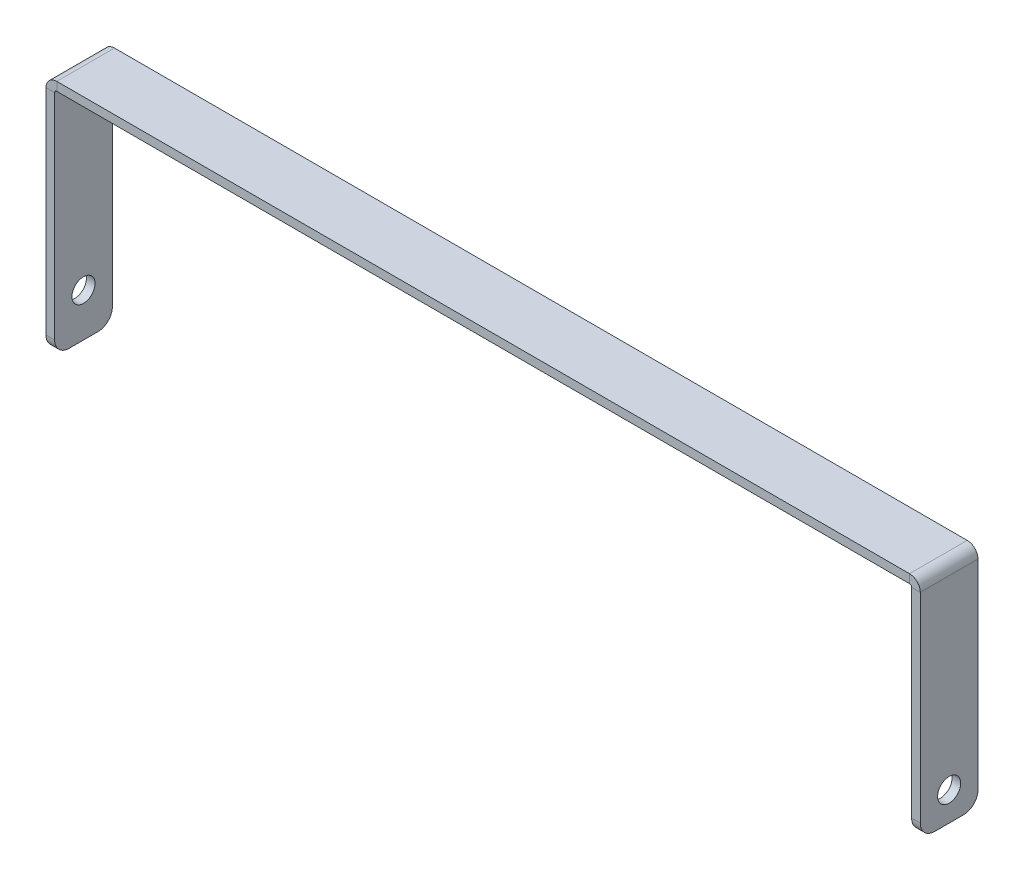
SolidWorks part; units mm, degrees
note: The reader was unsure of these and kept them because the rebuilt part matched: bend radius of "BaseBend1", "BaseBend2".
material "7079 Alloy"
ref_plane "Front" through (0, 0, 0) normal (0, 0, 1) x (1, 0, 0)
ref_plane "Top" through (0, 0, 0) normal (0, 1, 0) x (1, 0, 0)
ref_plane "Right" through (0, 0, 0) normal (1, 0, 0) x (0, 0, -1)
sketch "Sketch1" plane through (0, 0, 0) normal (0, 0, 1) x (1, 0, 0)
  line L0 (-148.5, -42.5) -> (-148.5, 37.5)
  line L1 (-148.5, 37.5) -> (148.5, 37.5)
  line L2 (148.5, 37.5) -> (148.5, -37.5)
  line L3 (148.5, -37.5) -> (-148.5, 37.5) construction
  dimension "D1" = 297
  dimension "D2" = 80
  dimension "D3" = 75
sheet metal parameters "Sheet-Metal1" thickness 3 parameters "D1"=0.7366
base flange "Base-Flange1" sketch "Sketch1" end condition mid plane depth 20 reverse direction no thickness 3 reverse thickness direction yes bend radius 0.7366
bend "BaseBend1" bend radius 0.7366 bend angle 90 parameters "D5"=1
bend "BaseBend2" bend radius 0.7366 bend angle 90 parameters "D5"=2
sketch "Sketch3" plane through (151.5, 0, 0) normal (1, 0, 0) x (0, 0, -1)
  line L0 (-10, -37.5) -> (10, -37.5) construction
  line L1 (10, 36.7634) -> (10, -37.5) construction
  circle A0 centre (0, -27.5) radius 4
  dimension "D2" = 8
  dimension "D3" = 10
  dimension "D1" = 10
extrude "Cut-Extrude1" cut sketch "Sketch3" against normal through all normal cut yes
fillet "Fillet1" radius 5 4 edges at (150, -37.5, -10) (150, -37.5, 10) (-150, -42.5, -10) (-150, -42.5, 10)
flat pattern "Flat-Pattern1" [suppressed]
sketch "Bend-Lines1" plane through (0, 40, 0) normal (0, 1, 0) x (-1, 0, 0)
  line L0 (146.7844, 10) -> (146.7844, -10) construction
  line L1 (-146.7844, 10) -> (-146.7844, -10) construction
bend of the flat pattern "Flatten-<BaseBend1>1"
bend of the flat pattern "Flatten-<BaseBend2>1"
